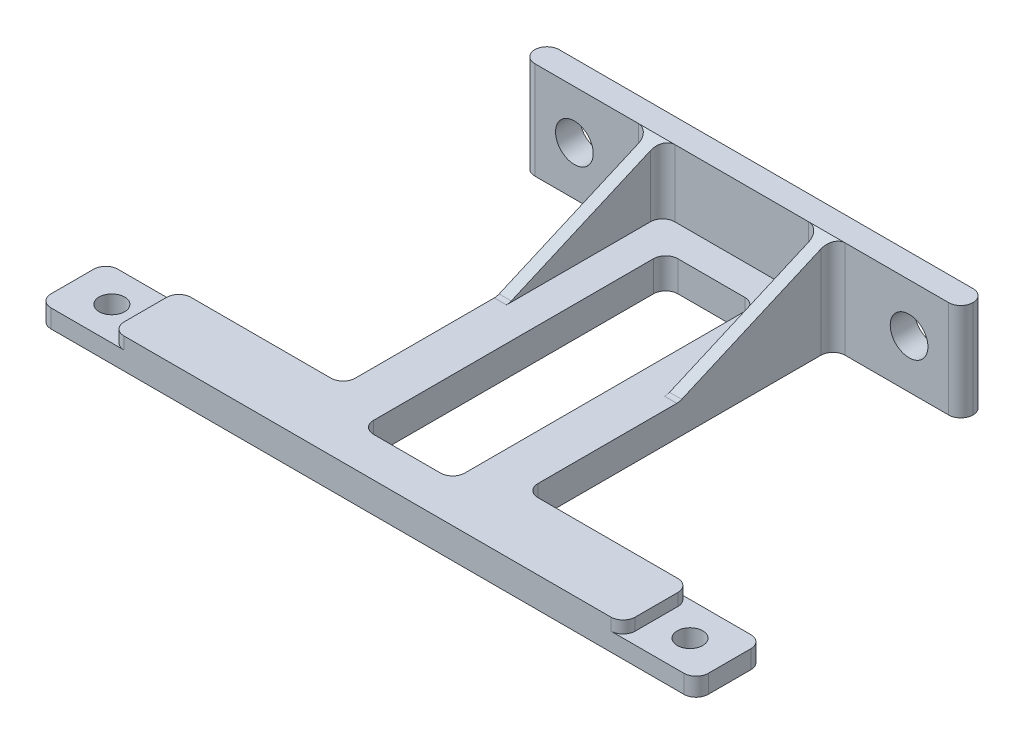
SolidWorks part; units mm, degrees
ref_plane "前视基准面" through (0, 0, 0) normal (0, 0, 1) x (1, 0, 0)
ref_plane "上视基准面" through (0, 0, 0) normal (0, 1, 0) x (1, 0, 0)
ref_plane "右视基准面" through (0, 0, 0) normal (1, 0, 0) x (0, 0, -1)
sketch "草图1" plane through (0, 0, 0) normal (0, 0, 1) x (1, 0, 0)
  line L0 (0, -341.5162) -> (0, 16734.2928) construction
  line L1 (-1000, 0) -> (49000, 0) construction
  line L2 (-36, -8) -> (36, -8)
  line L3 (-36, -8) -> (-36, 8)
  line L4 (-36, 8) -> (36, 8)
  line L5 (36, -8) -> (36, 8)
  line L6 (-36, -8) -> (36, 8) construction
  line L7 (-36, 8) -> (36, -8) construction
  circle A0 centre (-27.5, 0) radius 3.1
  circle A1 centre (27.5, 0) radius 3.1
  point P1 (0, 0)
  dimension "D2" = 6.2
  dimension "D3" = 27.5
  dimension "D1" = 16
  dimension "D4" = 72
extrude "凸台-拉伸1" add sketch "草图1" along normal blind 4
sketch "草图3" plane through (0, 0, 4) normal (0, 0, 1) x (1, 0, 0)
  line L0 (0, -1000) -> (0, 49000) construction
  line L1 (-36, -8) -> (36, -8) construction
  line L2 (-15, -3) -> (15, -3)
  line L3 (-15, -3) -> (-15, -8)
  line L4 (-15, -8) -> (15, -8)
  line L5 (15, -3) -> (15, -8)
  line L6 (-15, -3) -> (15, -8) construction
  line L7 (-15, -8) -> (15, -3) construction
  point P1 (0, -5.5)
  dimension "D1" = 5
  dimension "D2" = 30
extrude "凸台-拉伸2" add sketch "草图3" along normal blind 60 from surface starting at face at (-24.4, 0, 0)
sketch "草图5" plane through (0, -3, 0) normal (0, 1, 0) x (1, 0, 0)
  line L0 (-1007.641, -60) -> (48992.359, -60) construction
  line L2 (15, -60) -> (-15, -60) construction
  line L4 (0, -989.2683) -> (0, 48741.716) construction
  line L5 (-54, -65.5) -> (54, -65.5)
  line L6 (-54, -65.5) -> (-54, -54.5)
  line L7 (-54, -54.5) -> (54, -54.5)
  line L8 (54, -65.5) -> (54, -54.5)
  line L9 (-54, -65.5) -> (54, -54.5) construction
  line L10 (-54, -54.5) -> (54, -65.5) construction
  circle A0 centre (47.5, -60) radius 2.1
  circle A1 centre (-47.5, -60) radius 2.1
  point P7 (0, -60)
  point P16 (-10.8576, -60)
  dimension "D1" = 4.2
  dimension "D2" = 47.5
  dimension "D3" = 11
  dimension "D4" = 108
extrude "凸台-拉伸3" add sketch "草图5" against normal through all
sketch "草图6" plane through (0, -3, 0) normal (0, 1, 0) x (1, 0, 0)
  line L0 (-15, -54.5) -> (-54, -54.5) construction
  line L2 (0, -1000) -> (0, 49000) construction
  line L3 (-54, -65.5) -> (-42, -65.5)
  line L4 (-54, -65.5) -> (-54, -54.5)
  line L5 (-54, -54.5) -> (-42, -54.5)
  line L6 (-42, -65.5) -> (-42, -54.5)
  line L7 (54, -54.5) -> (42, -54.5)
  line L8 (42, -65.5) -> (42, -54.5)
  line L9 (54, -65.5) -> (42, -65.5)
  line L10 (54, -65.5) -> (54, -54.5)
  dimension "D1" = 12
extrude "切除-拉伸1" cut sketch "草图6" against normal blind 2
sketch "草图7" plane through (0, -3, 0) normal (0, 1, 0) x (1, 0, 0)
  line L0 (0, -1000) -> (0, 49000) construction
  line L1 (36, -4) -> (-36, -4) construction
  line L2 (-7.5, -59) -> (7.5, -59)
  line L3 (-7.5, -59) -> (-7.5, -9)
  line L4 (-7.5, -9) -> (7.5, -9)
  line L5 (7.5, -59) -> (7.5, -9)
  line L6 (-7.5, -59) -> (7.5, -9) construction
  line L7 (-7.5, -9) -> (7.5, -59) construction
  point P1 (0, -34)
  dimension "D1" = 15
  dimension "D2" = 50
  dimension "D3" = 5
extrude "切除-拉伸2" cut sketch "草图7" against normal through all
sketch "草图8" plane through (-15, 0, 0) normal (-1, 0, 0) x (0, 0, 1)
  line L0 (4, -3) -> (29.25, -3)
  line L1 (54.5, -3) -> (4, -3) construction
  line L2 (29.25, -3) -> (4, 8)
  line L3 (4, 8) -> (4, -3)
extrude "凸台-拉伸4" add sketch "草图8" against normal blind 2
extrude "凸台-拉伸5" add sketch "草图8<2>" along normal blind 2 from surface starting at face at (15, -5.5, 29.25)
sketch "草图8<2>" plane through (-15, 0, 0) normal (-1, 0, 0) x (0, 0, 1) same geometry as "草图8"
fillet "圆角1" radius 2 24 edges at (15, 0, 4) (36, 0, 4) (36, 0, 0) (-36, 0, 0) (-36, 0, 4) (-15, -5.5, 54.5) (-54, -6.5, 54.5) (-54, -6.5, 65.5) (54, -6.5, 65.5) (54, -6.5, 54.5) (15, -5.5, 54.5) (-15, 0, 4) (-42, -4, 54.5) (42, -4, 54.5) (42, -4, 65.5) (-42, -4, 65.5) (-7.5, -5.5, 59) (-7.5, -5.5, 9) (7.5, -5.5, 59) (7.5, -5.5, 9) (14, -3, 29.25) (-14, -3, 29.25) (-13, 2.5, 4) (13, 2.5, 4)
